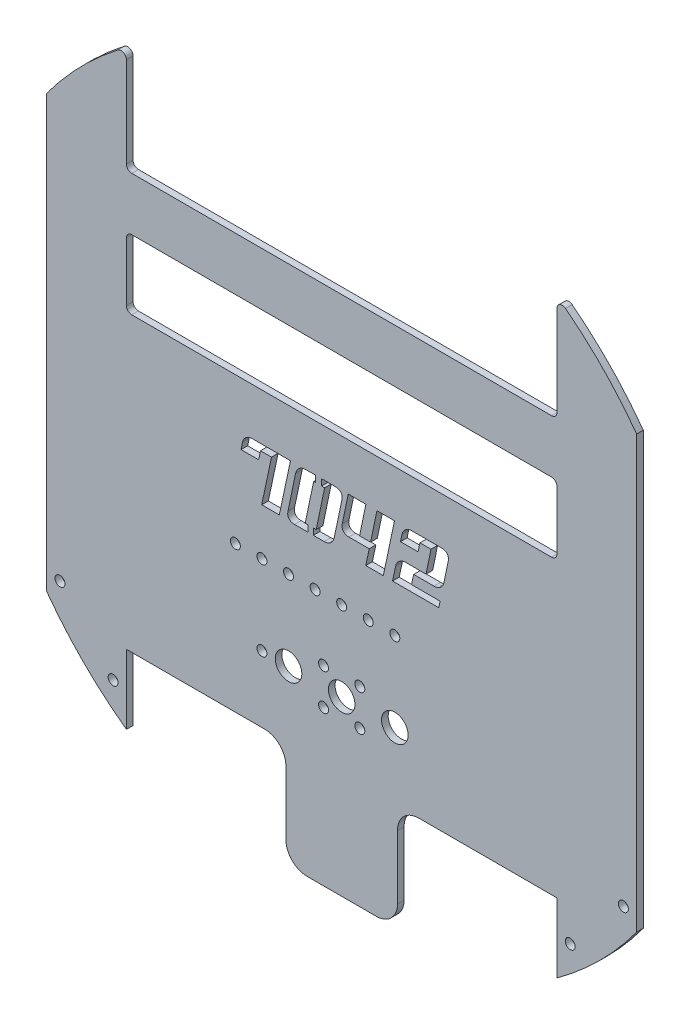
SolidWorks part; units mm, degrees
material "6061 Alloy"
ref_plane "Front Plane" through (0, 0, 0) normal (0, 0, 1) x (1, 0, 0)
ref_plane "Top Plane" through (0, 0, 0) normal (0, 1, 0) x (1, 0, 0)
ref_plane "Right Plane" through (0, 0, 0) normal (1, 0, 0) x (0, 0, -1)
sketch "Sketch1" plane through (0, 0, 0) normal (0, 0, 1) x (1, 0, 0)
  line L1 (-140.9655, 145.0225) -> (-102.8655, 145.0225)
  line L2 (-140.9655, 145.0225) -> (-140.9655, -145.0225)
  line L3 (-140.9655, -145.0225) -> (-102.8655, -145.0225)
  line L4 (-102.8655, 145.0225) -> (-102.8655, -145.0225)
  line L5 (-140.9655, 145.0225) -> (-102.8655, -145.0225) construction
  line L6 (-140.9655, -145.0225) -> (-102.8655, 145.0225) construction
  line L7 (-140.9655, 31.75) -> (140.9655, 31.75)
  line L8 (-140.9655, 31.75) -> (-140.9655, -31.75)
  line L9 (-140.9655, -31.75) -> (140.9655, -31.75)
  line L10 (140.9655, 31.75) -> (140.9655, -31.75)
  line L11 (-140.9655, 31.75) -> (140.9655, -31.75) construction
  line L12 (-140.9655, -31.75) -> (140.9655, 31.75) construction
  line L13 (102.8655, 145.0225) -> (140.9655, 145.0225)
  line L14 (102.8655, 145.0225) -> (102.8655, -145.0225)
  line L15 (102.8655, -145.0225) -> (140.9655, -145.0225)
  line L16 (140.9655, 145.0225) -> (140.9655, -145.0225)
  line L17 (102.8655, 145.0225) -> (140.9655, -145.0225) construction
  line L18 (102.8655, -145.0225) -> (140.9655, 145.0225) construction
  line L19 (-140.9655, -31.75) -> (140.9655, -31.75)
  line L20 (-140.9655, -31.75) -> (-140.9655, -69.85)
  line L21 (-140.9655, -69.85) -> (140.9655, -69.85)
  line L22 (140.9655, -31.75) -> (140.9655, -69.85)
  circle A0 centre (0, 0) radius 177.8
  circle A7 centre (0, -38.1) radius 25.4 construction
  circle A8 centre (-25.4, -38.1) radius 2.3813
  circle A9 centre (25.4, -38.1) radius 2.3813
  circle A10 centre (0, -38.1) radius 2.3812
  point P3 (-121.9155, 0)
  point P12 (121.9155, 0)
  dimension "D1" = 355.6
  dimension "D5" = 50.8
  dimension "D6" = 38.1
  dimension "D7" = 281.9311
  dimension "D10" = 4.7625
  dimension "D8" = 4.7625
  dimension "D9" = 4.7625
  dimension "D2" = 38.1
  dimension "D3" = 38.1
  dimension "D4" = 63.5
  dimension "D12" = 38.1
extrude "Boss-Extrude1" add sketch "Sketch1" along normal blind 3.175 contours L4 A0 L2 L7 | L2 L9 L4 L7 | L14 L7 L4 L9 A8 | L2 A0 L4 L9 | L16 A0 L14 L7 | L7 L14 L9 L10 | L14 A0 L16 L9 | L19 A10 L9 L4 L21 L14 A9 A8 | L2 L21 L4 L9 | L14 L21 L16 L9 region at (-120.723, 80.7079, 0) region at (0, 0, 0) region at (-121.9155, 0, 0) region at (120.723, 80.7079, 0) region at (-119.9486, -100.1295, 0) region at (0, -50.8872, 0) region at (-121.9155, -50.8, 0) region at (121.9155, 0, 0) region at (121.9155, -50.8, 0) region at (119.9486, -100.1295, 0)
sketch "Sketch2" plane through (0, 0, 3.175) normal (0, 0, 1) x (1, 0, 0)
  line L0 (-140.9655, -103.066) -> (-140.9655, -108.3585)
  line L1 (-140.9655, 108.3585) -> (-140.9655, -108.3585) construction
  line L2 (-102.8655, -141.1119) -> (-102.8655, -145.0225)
  line L3 (102.8655, -141.1119) -> (102.8655, -145.0225)
  line L4 (102.8655, -69.85) -> (102.8655, -145.0225) construction
  line L5 (140.9655, -103.066) -> (140.9655, -108.3585)
  line L6 (140.9655, 108.3585) -> (140.9655, -108.3585) construction
  line L7 (-102.8655, -69.85) -> (-102.8655, -145.0225) construction
  circle A0 centre (0, 0) radius 177.8
  circle A1 centre (0, 0) radius 174.625
  line M3 (-140.9655, 108.3585) -> (-140.9655, -108.3585)
  arc M4 (-140.9655, -108.3585) -> (-102.8655, -145.0225) centre (0, 0) ccw
  line M5 (-102.8655, -145.0225) -> (-102.8655, -69.85)
  line M7 (102.8655, -69.85) -> (102.8655, -145.0225)
  arc M8 (102.8655, -145.0225) -> (140.9655, -108.3585) centre (0, 0) ccw
  line M9 (140.9655, -108.3585) -> (140.9655, 108.3585)
  dimension "D1" = 355.6
  dimension "D2" = 349.25
extrude "Boss-Extrude2" add sketch "Sketch2" along normal blind 50.8 contours A1 M3 M4 M5 | A1 M7 M8 M9 region at (-122.8631, -125.3578, 3.175) region at (122.8631, -125.3578, 3.175)
sketch "Sketch3" plane through (0, 0, 3.175) normal (0, 0, 1) x (1, 0, 0)
  circle A0 centre (0, 0) radius 174.625
  circle A1 centre (0, 0) radius 203.8293
  dimension "D1" = 349.25
extrude "Cut-Extrude1" cut sketch "Sketch3" along normal through all and the other way through all
sketch "Sketch5" plane through (0, 0, 3.175) normal (0, 0, 1) x (1, 0, 0)
  line L0 (0, 165.1) -> (0, -165.1) construction
  line L1 (102.8655, -69.85) -> (102.8655, -141.1119) construction
  circle A0 centre (0, 0) radius 165.1 construction
  circle A1 centre (134.6155, -95.5859) radius 2.3813
  circle A2 centre (109.2155, -123.8143) radius 2.3813
  circle A3 centre (-134.6155, -95.5859) radius 2.3813
  circle A4 centre (-109.2155, -123.8143) radius 2.3813
  arc A5 (140.9655, 103.066) -> (102.8655, 141.1119) centre (0, 0) ccw construction
  dimension "D1" = 330.2
  dimension "D3" = 4.7625
  dimension "D4" = 4.7625
  dimension "D2" = 25.4
  dimension "D5" = 6.35
extrude "Cut-Extrude3" cut sketch "Sketch5" against normal through all
sketch "Sketch6" plane through (0, 0, 3.175) normal (0, 0, 1) x (1, 0, 0)
  line L0 (-102.8655, 141.1119) -> (-102.8655, 31.75) construction
  line L1 (-102.8655, 90.3119) -> (102.8655, 90.3119)
  line L2 (-102.8655, 90.3119) -> (-102.8655, 64.9119)
  line L3 (-102.8655, 64.9119) -> (102.8655, 64.9119)
  line L4 (102.8655, 90.3119) -> (102.8655, 64.9119)
  line L5 (102.8655, 141.1119) -> (102.8655, 31.75) construction
  dimension "D1" = 25.4
  dimension "D2" = 50.8
extrude "Boss-Extrude3" add sketch "Sketch6" against normal blind 3.175
sketch "Sketch7" plane through (0, 0, 3.175) normal (0, 0, 1) x (1, 0, 0)
  line L0 (102.8655, 90.3119) -> (-102.8655, 90.3119) construction
  line L1 (-157.8266, 90.3119) -> (153.0605, 90.3119)
  line L2 (-157.8266, 90.3119) -> (-157.8266, 162.3702)
  line L3 (-157.8266, 162.3702) -> (153.0605, 162.3702)
  line L4 (153.0605, 90.3119) -> (153.0605, 162.3702)
extrude "Cut-Extrude4" [suppressed] cut sketch "Sketch7" against normal through all
sketch "Sketch8" plane through (0, 0, 3.175) normal (0, 0, 1) x (1, 0, 0)
  circle A0 centre (0, -38.1) radius 38.1 construction
  circle A1 centre (-38.1, -38.1) radius 2.3812
  circle A2 centre (0, -38.1) radius 50.8 construction
  circle A3 centre (-50.8, -38.1) radius 2.3812
  circle A4 centre (0, -38.1) radius 12.7 construction
  circle A5 centre (12.7, -38.1) radius 2.3812
  circle A6 centre (-12.7, -38.1) radius 2.3812
  dimension "D1" = 76.2
  dimension "D2" = 4.7625
  dimension "D3" = 101.6
  dimension "D4" = 4.7625
  dimension "D5" = 25.4
  dimension "D6" = 4.7625
  dimension "D7" = 4.7625
extrude "Cut-Extrude5" cut sketch "Sketch8" against normal through all
sketch "Sketch9" plane through (0, 0, 3.175) normal (0, 0, 1) x (1, 0, 0)
  line L0 (102.8655, -69.85) -> (102.8655, -141.1119) construction
  line L1 (-102.8655, -69.85) -> (102.8655, -69.85)
  line L2 (-102.8655, -69.85) -> (-102.8655, -107.95)
  line L3 (-102.8655, -107.95) -> (102.8655, -107.95)
  line L4 (102.8655, -69.85) -> (102.8655, -107.95)
  dimension "D1" = 38.1
extrude "Boss-Extrude4" add sketch "Sketch9" against normal blind 3.175
sketch "Sketch10" plane through (0, 0, 3.175) normal (0, 0, 1) x (1, 0, 0)
  circle A0 centre (0, -76.2) radius 6.35
  circle A1 centre (0, -38.1) radius 2.3812 construction
  circle A2 centre (0, -76.2) radius 25.4 construction
  circle A3 centre (0, -76.2) radius 38.1 construction
  circle A4 centre (-25.4, -76.2) radius 2.3813
  circle A5 centre (-38.1, -76.2) radius 2.3812
  circle A6 centre (25.4, -76.2) radius 2.3813
  dimension "D1" = 38.1
  dimension "D2" = 12.7
  dimension "D3" = 50.8
  dimension "D4" = 76.2
  dimension "D5" = 4.7625
  dimension "D6" = 4.7625
  dimension "D7" = 4.7625
extrude "Cut-Extrude6" cut sketch "Sketch10" against normal through all
sketch "Sketch11" plane through (0, 0, 3.175) normal (0, 0, 1) x (1, 0, 0)
  line L0 (-102.8655, -107.95) -> (102.8655, -107.95) construction
  line L1 (-26.6655, -107.95) -> (26.6655, -107.95)
  line L2 (-26.6655, -107.95) -> (-26.6655, -158.75)
  line L3 (-26.6655, -158.75) -> (26.6655, -158.75)
  line L4 (26.6655, -107.95) -> (26.6655, -158.75)
  line L5 (-102.8655, -107.95) -> (-102.8655, -141.1119) construction
  line L6 (102.8655, -107.95) -> (102.8655, -141.1119) construction
  dimension "D1" = 50.8
  dimension "D2" = 76.2
  dimension "D3" = 76.2
extrude "Boss-Extrude5" add sketch "Sketch11" against normal blind 3.175
fillet "Fillet1" radius 10.16 4 edges at (26.6655, -107.95, 1.5875) (-26.6655, -107.95, 1.5875) (-26.6655, -158.75, 1.5875) (26.6655, -158.75, 1.5875)
sketch "Sketch12" plane through (0, 0, 3.175) normal (0, 0, 1) x (1, 0, 0)
  line L1 (-12.7, -63.5) -> (12.7, -63.5) construction
  line L2 (-12.7, -63.5) -> (-12.7, -88.9) construction
  line L3 (-12.7, -88.9) -> (12.7, -88.9) construction
  line L4 (12.7, -63.5) -> (12.7, -88.9) construction
  circle A0 centre (-25.4, -76.2) radius 6.35
  circle A1 centre (25.4, -76.2) radius 6.35
  circle A2 centre (0, -76.2) radius 6.35 construction
  circle A3 centre (-8.6678, -67.5323) radius 2.3812
  circle A7 centre (8.6677, -67.5322) radius 2.3813
  circle A8 centre (8.6678, -84.8677) radius 2.3812
  circle A9 centre (-8.6677, -84.8677) radius 2.3812
  point P23 (0, -76.2)
  point P24 (0, -76.2)
  dimension "D1" = 12.7
  dimension "D2" = 12.7
  dimension "D7" = 4.0323
  dimension "D9" = 4.7625
  dimension "D3" = 12.7
  dimension "D4" = 25.4
  dimension "D5" = 12.7
  dimension "D6" = 25.4
  dimension "D8" = 4.0323
  dimension "D10" = 4
extrude "Cut-Extrude7" cut sketch "Sketch12" against normal through all
fillet "Fillet2" radius 2.54 2 edges at (102.8655, 141.1119, 1.5875) (-102.8655, 141.1119, 1.5875)
sketch "Sketch13" plane through (0, 0, 3.175) normal (0, 0, 1) x (1, 0, 0)
  line L0 (-140.9655, -16.1069) -> (140.9655, -16.1069) construction
  line L1 (-140.9655, 103.066) -> (-140.9655, -103.066) construction
  line L2 (140.9655, 103.066) -> (140.9655, -103.066) construction
  text T0 "7042" font "Aero" height 25.4
extrude "Cut-Extrude8" cut sketch "Sketch13" against normal through all
sketch "Sketch14" plane through (0, 0, 3.175) normal (0, 0, 1) x (1, 0, 0)
  line L1 (-12.3972, 11.8715) -> (-9.6379, 11.8715)
  line L2 (-12.3972, 11.8715) -> (-12.3972, 3.9079)
  line L3 (-12.3972, 3.9079) -> (-9.6379, 3.9079)
  line L4 (-9.6379, 11.8715) -> (-9.6379, 3.9079)
  line L5 (-16.0587, -11.8105) -> (-13.5317, -11.8105)
  line L6 (-16.0587, -11.8105) -> (-16.0587, -17.7494)
  line L7 (-16.0587, -17.7494) -> (-13.5317, -17.7494)
  line L8 (-13.5317, -11.8105) -> (-13.5317, -17.7494)
extrude "Boss-Extrude6" add sketch "Sketch14" against normal blind 3.175
fillet "Fillet3" radius 2.54 6 edges at (-102.8655, 90.3119, 1.5875) (102.8655, 90.3119, 1.5875) (102.8655, 31.75, 1.5875) (102.8655, 64.9119, 1.5875) (-102.8655, 31.75, 1.5875) (-102.8655, 64.9119, 1.5875)
